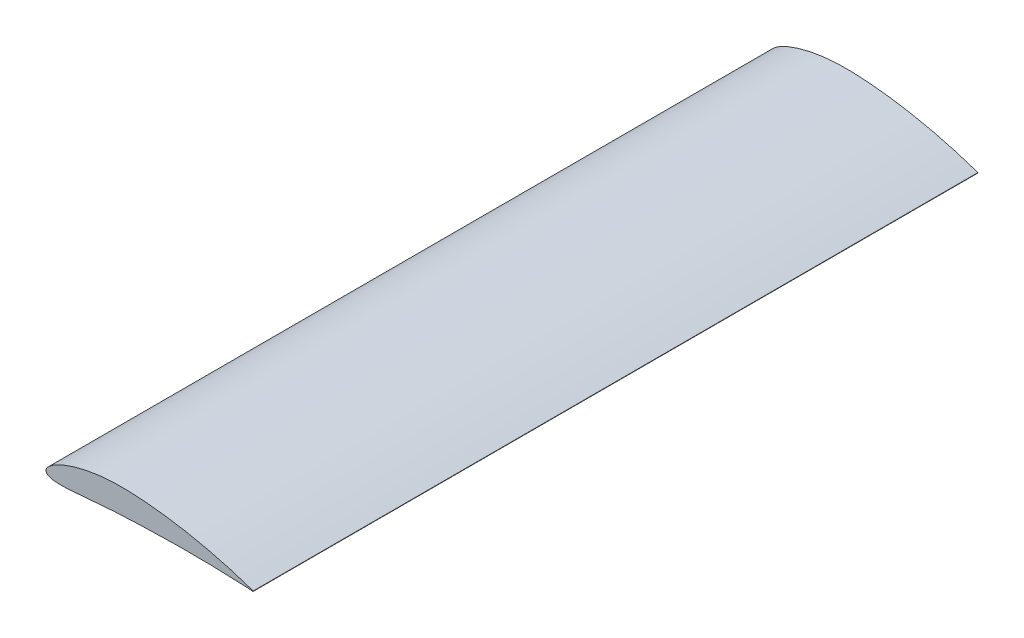
SolidWorks part; units mm, degrees
ref_plane "Front Plane" through (0, 0, 0) normal (0, 0, 1) x (1, 0, 0)
ref_plane "Top Plane" through (0, 0, 0) normal (0, 1, 0) x (1, 0, 0)
ref_plane "Right Plane" through (0, 0, 0) normal (1, 0, 0) x (0, 0, -1)
curve "Curve2"
  spline degree 3 poles (1000.25, 1.24, 0) (999.36, 1.5466, 0) (995.8139, 2.7683, 0) (987.8762, 5.5077, 0) (974.7136, 9.9275, 0) (956.465, 15.9446, 0) (933.2861, 23.3123, 0) (905.3935, 31.8009, 0) (873.0611, 41.1442, 0) (836.5996, 51.0483, 0) (796.3762, 61.2143, 0) (752.7953, 71.3209, 0) (706.3231, 81.1144, 0) (657.4446, 90.2776, 0) (606.6871, 98.541, 0) (554.6079, 105.6901, 0) (501.792, 111.4952, 0) (448.8062, 115.7722, 0) (395.8896, 118.5809, 0) (343.6082, 118.9114, 0) (292.6925, 116.357, 0) (244.199, 111.1728, 0) (198.7693, 103.6648, 0) (157.0012, 94.1608, 0) (119.4181, 83.1247, 0) (86.4596, 71.0512, 0) (58.48, 58.4287, 0) (35.7445, 45.7437, 0) (18.354, 33.4445, 0) (6.4016, 21.7983, 0) (-0.4785, 10.7687, 0) (-1.1021, -0.3322, 0) (5.4783, -9.2258, 0) (17.0143, -14.7948, 0) (32.8747, -18.4511, 0) (53.3085, -20.3675, 0) (78.1118, -20.7512, 0) (107.0475, -19.7633, 0) (139.7896, -17.6475, 0) (176.0022, -14.654, 0) (215.3329, -11.125, 0) (257.4273, -7.3624, 0) (301.9209, -3.6922, 0) (348.4441, -0.4557, 0) (396.9816, 1.9832, 0) (447.1013, 3.7059, 0) (498.2783, 5.4818, 0) (549.6221, 6.9005, 0) (600.5599, 7.9279, 0) (650.5484, 8.5041, 0) (699.0372, 8.6069, 0) (745.4858, 8.2663, 0) (789.3705, 7.5598, 0) (830.1852, 6.5089, 0) (867.4516, 5.2968, 0) (900.7439, 3.9432, 0) (929.5972, 2.6539, 0) (953.857, 1.2862, 0) (972.6764, 0.624, 0) (987.1696, -1.0584, 0) (994.3521, -0.0144, 0) (999.8798, -2.0481, 0) (999.9716, -0.4847, 0) (1000, 0, 0) knots 0 0 0 0 0.001372 0.005465 0.012235 0.021602 0.033461 0.047671 0.064081 0.082496 0.102719 0.124527 0.147676 0.171913 0.196978 0.222597 0.248497 0.274385 0.300041 0.32569 0.350525 0.37428 0.396711 0.417577 0.436654 0.453744 0.46868 0.481329 0.491631 0.499616 0.505546 0.510185 0.514824 0.520702 0.528516 0.538466 0.550543 0.564643 0.580638 0.598345 0.617584 0.638174 0.659922 0.682632 0.706121 0.730727 0.7557 0.780732 0.805564 0.829932 0.85357 0.876213 0.89761 0.917519 0.935698 0.951943 0.966047 0.97784 0.987174 0.993932 0.998018 0.999386 1 1 1 1
sketch "Sketch1" plane through (0, 0, 0) normal (0, 0, 1) x (1, 0, 0)
  arc A0 (1000.25, 1.24) -> (1000, 0) centre (1000.0422, 0.6367) cw
  spline S0 degree 3 poles (856.9359, -2933.2024) (1505.4694, -162.2574) (1247.2352, -84.0002) (987.8762, 5.5077) (974.7136, 9.9275) (956.465, 15.9446) (933.2861, 23.3123) (905.3935, 31.8009) (873.0611, 41.1442) (836.5996, 51.0483) (796.3762, 61.2143) (752.7953, 71.3209) (706.3231, 81.1144) (657.4446, 90.2776) (606.6871, 98.541) (554.6079, 105.6901) (501.792, 111.4952) (448.8062, 115.7722) (395.8896, 118.5809) (343.6082, 118.9114) (292.6925, 116.357) (244.199, 111.1728) (198.7693, 103.6648) (157.0012, 94.1608) (119.4181, 83.1247) (86.4596, 71.0512) (58.48, 58.4287) (35.7445, 45.7437) (18.354, 33.4445) (6.4016, 21.7983) (-0.4785, 10.7687) (-1.1021, -0.3322) (5.4783, -9.2258) (17.0143, -14.7948) (32.8747, -18.4511) (53.3085, -20.3675) (78.1118, -20.7512) (107.0475, -19.7633) (139.7896, -17.6475) (176.0022, -14.654) (215.3329, -11.125) (257.4273, -7.3624) (301.9209, -3.6922) (348.4441, -0.4557) (396.9816, 1.9832) (447.1013, 3.7059) (498.2783, 5.4818) (549.6221, 6.9005) (600.5599, 7.9279) (650.5484, 8.5041) (699.0372, 8.6069) (745.4858, 8.2663) (789.3705, 7.5598) (830.1852, 6.5089) (867.4516, 5.2968) (900.7439, 3.9432) (929.5972, 2.6539) (953.857, 1.2862) (972.6764, 0.624) (987.1696, -1.0584) (994.3521, -0.0144) (1012.3874, -6.6496) (918.9793, 128.1334) (2840.5265, -2357.9075) knots -0.387528 -0.387528 -0.387528 -0.387528 0.001372 0.005465 0.012235 0.021602 0.033461 0.047671 0.064081 0.082496 0.102719 0.124527 0.147676 0.171913 0.196978 0.222597 0.248497 0.274385 0.300041 0.32569 0.350525 0.37428 0.396711 0.417577 0.436654 0.453744 0.46868 0.481329 0.491631 0.499616 0.505546 0.510185 0.514824 0.520702 0.528516 0.538466 0.550543 0.564643 0.580638 0.598345 0.617584 0.638174 0.659922 0.682632 0.706121 0.730727 0.7557 0.780732 0.805564 0.829932 0.85357 0.876213 0.89761 0.917519 0.935698 0.951943 0.966047 0.97784 0.987174 0.993932 0.998018 0.999386 1.013731 1.013731 1.013731 1.013731 only from (1000.25, 1.24) to (1000, 0) construction
  spline S1 degree 3 poles (1000.25, 1.24) (999.36, 1.5466) (995.8139, 2.7683) (987.8762, 5.5077) (974.7136, 9.9275) (956.465, 15.9446) (933.2861, 23.3123) (905.3935, 31.8009) (873.0611, 41.1442) (836.5996, 51.0483) (796.3762, 61.2143) (752.7953, 71.3209) (706.3231, 81.1144) (657.4446, 90.2776) (606.6871, 98.541) (554.6079, 105.6901) (501.792, 111.4952) (448.8062, 115.7722) (395.8896, 118.5809) (343.6082, 118.9114) (292.6925, 116.357) (244.199, 111.1728) (198.7693, 103.6648) (157.0012, 94.1608) (119.4181, 83.1247) (86.4596, 71.0512) (58.48, 58.4287) (35.7445, 45.7437) (18.354, 33.4445) (6.4016, 21.7983) (-0.4785, 10.7687) (-1.1021, -0.3322) (5.4783, -9.2258) (17.0143, -14.7948) (32.8747, -18.4511) (53.3085, -20.3675) (78.1118, -20.7512) (107.0475, -19.7633) (139.7896, -17.6475) (176.0022, -14.654) (215.3329, -11.125) (257.4273, -7.3624) (301.9209, -3.6922) (348.4441, -0.4557) (396.9816, 1.9832) (447.1013, 3.7059) (498.2783, 5.4818) (549.6221, 6.9005) (600.5599, 7.9279) (650.5484, 8.5041) (699.0372, 8.6069) (745.4858, 8.2663) (789.3705, 7.5598) (830.1852, 6.5089) (867.4516, 5.2968) (900.7439, 3.9432) (929.5972, 2.6539) (953.857, 1.2862) (972.6764, 0.624) (987.1696, -1.0584) (994.3521, -0.0144) (999.8798, -2.0481) (999.9716, -0.4847) (1000, 0) knots 0 0 0 0 0.001372 0.005465 0.012235 0.021602 0.033461 0.047671 0.064081 0.082496 0.102719 0.124527 0.147676 0.171913 0.196978 0.222597 0.248497 0.274385 0.300041 0.32569 0.350525 0.37428 0.396711 0.417577 0.436654 0.453744 0.46868 0.481329 0.491631 0.499616 0.505546 0.510185 0.514824 0.520702 0.528516 0.538466 0.550543 0.564643 0.580638 0.598345 0.617584 0.638174 0.659922 0.682632 0.706121 0.730727 0.7557 0.780732 0.805564 0.829932 0.85357 0.876213 0.89761 0.917519 0.935698 0.951943 0.966047 0.97784 0.987174 0.993932 0.998018 0.999386 1 1 1 1
extrude "Boss-Extrude1" add sketch "Sketch1" along normal blind 7000 contours S1 A0
scale "Scale1" bodies to scale 101 scale about origin uniform scaling no x scale factor 2 y scale factor 2 z scale factor 1
ref_axis "Axis1" through (2000.5, 2.48, 7000) along (0, 0, -1)
ref_plane "Plane1" through (2000.5, 0, 0) normal (1, 0, 0) x (0, 0, -1)
sketch "Sketch2" plane through (0, 0, 7000) normal (0, 0, 1) x (1, 0, 0)
  line L0 (0, 0) -> (2000.5, 2.48)
ref_axis "Axis2" through (-4598.815, -5.7011, 7000) along (1, 0.0012, 0)
ref_point "Point1"
ref_plane "Plane2" through (0, 0, 7000) normal (0, 0, -1) x (1, 0.0012, 0)
ref_plane "Plane4" through (0, 0, 6000) normal (0, 0, -1) x (1, 0.0012, 0)
ref_axis "Axis3" through (2101.5387, 0, 6000) along (-1, 0, 0)
ref_point "Point2"
ref_plane "Plane5" through (0, 0, 1000) normal (0, 0, -1) x (1, 0.0012, 0)
ref_axis "Axis4" through (2101.5387, 0, 1000) along (-1, 0, 0)
ref_point "Point3"
ref_plane "Plane6" through (1600.5, 0, 0) normal (1, 0, 0) x (0, 0, -1)
ref_point "Point4"
ref_point "Point5"
